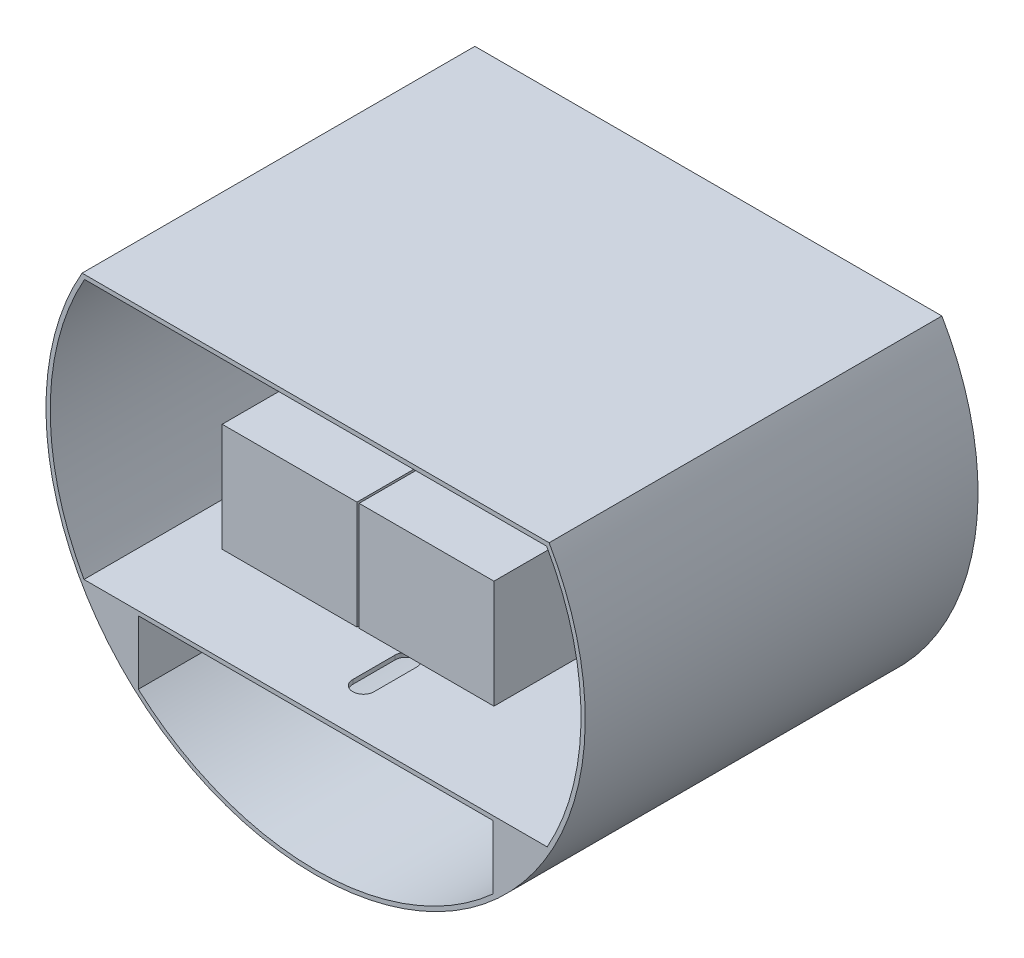
SolidWorks part; units mm, degrees
ref_plane "Front Plane" through (0, 0, 0) normal (0, 0, 1) x (1, 0, 0)
ref_plane "Top Plane" through (0, 0, 0) normal (0, 1, 0) x (1, 0, 0)
ref_plane "Right Plane" through (0, 0, 0) normal (1, 0, 0) x (0, 0, -1)
sketch "Sketch4" plane through (0, 0, 0) normal (0, 0, 1) x (1, 0, 0)
  line L0 (-109.9852, 63.5) -> (109.9852, 63.5)
  arc A0 (-109.9852, 63.5) -> (109.9852, 63.5) centre (0, 0) ccw
  point P5 (0, 63.5)
  dimension "D1" = 254
  dimension "D2" = 63.5
extrude "Exterior" add sketch "Sketch4" along normal blind 185 contours A0 L0
shell "Shell3" thickness 2 removed face at (0, -31.75, 0) removed face at (0, -31.75, 185)
sketch "Sketch7" plane through (0, 0, 0) normal (0, 0, 1) x (1, 0, 0)
  line L0 (-109.0942, -61.0202) -> (109.0942, -61.0202)
  line L1 (-83.5, -63.0202) -> (-83.5, -93.0202)
  line L2 (0, 0) -> (0, -138.9395) construction
  line L3 (83.5, -63.0202) -> (83.5, -93.0202)
  line L4 (-83.5, -63.0202) -> (83.5, -63.0202)
  arc A0 (-108.8244, 61.5) -> (108.8244, 61.5) centre (0, 0) ccw construction
  arc A1 (-109.0942, -61.0202) -> (-83.5, -93.0202) centre (0, 0) ccw
  arc A2 (83.5, -93.0202) -> (109.0942, -61.0202) centre (0, 0) ccw
  dimension "D1" = 83.5
  dimension "D2" = 2
  dimension "D3" = 30
extrude "Boss-Extrude4" add sketch "Sketch7" along normal up to surface (185 mm away) up to face at (0, -31.75, 185)
sketch "Sketch6" plane through (0, 0, 0) normal (0, 0, 1) x (1, 0, 0)
  line L0 (-64, -36.1655) -> (-0.5, -36.1655)
  line L1 (-0.5, -36.1655) -> (-0.5, 14.8345)
  line L2 (-0.5, 14.8345) -> (-64, 14.8345)
  line L3 (-64, 14.8345) -> (-64, -36.1655)
  line L12 (0.5, -36.1655) -> (64, -36.1655)
  line L13 (64, -36.1655) -> (64, 14.8345)
  line L14 (64, 14.8345) -> (0.5, 14.8345)
  line L15 (0.5, 14.8345) -> (0.5, -36.1655)
  line L20 (-0.5, 14.8345) -> (0.5, 14.8345) construction
  point P8 (0, 14.8345)
  dimension "D1" = 63.5
  dimension "D2" = 51
  dimension "D3" = 1
extrude "Batteries" add sketch "Sketch6" along normal blind 165 separate body
sketch "Sketch8" plane through (0, -61.0202, 0) normal (0, 1, 0) x (1, 0, 0)
  line L0 (-5, -22.5) -> (-5, -42.5)
  line L1 (-5, -62.5) -> (-5, -82.5)
  line L2 (-5, -82.5) -> (-5, -102.5) construction
  line L3 (-5, -102.5) -> (-5, -122.5)
  line L4 (-109.0942, -185) -> (-109.0942, 0) construction
  line L5 (-5, -142.5) -> (-5, -162.5)
  line L6 (-109.0942, -185) -> (-109.0942, 0) construction
  line L7 (5, -22.5) -> (5, -42.5)
  line L8 (5, -62.5) -> (5, -82.5)
  line L9 (5, -102.5) -> (5, -122.5)
  line L10 (5, -142.5) -> (5, -162.5)
  line L11 (-5, -22.5) -> (5, -22.5) construction
  line L12 (-5, -42.5) -> (5, -42.5) construction
  line L13 (-5, -142.5) -> (5, -142.5) construction
  line L14 (-5, -62.5) -> (5, -62.5) construction
  line L16 (-5, -82.5) -> (5, -82.5) construction
  arc A0 (5, -22.5) -> (-5, -22.5) centre (0, -22.5) ccw
  arc A1 (-5, -42.5) -> (5, -42.5) centre (0, -42.5) ccw
  arc A2 (5, -62.5) -> (-5, -62.5) centre (0, -62.5) ccw
  arc A3 (-5, -82.5) -> (5, -82.5) centre (0, -82.5) ccw
  arc A4 (5, -102.5) -> (-5, -102.5) centre (0, -102.5) ccw
  arc A5 (-5, -122.5) -> (5, -122.5) centre (0, -122.5) ccw
  arc A7 (-5, -162.5) -> (5, -162.5) centre (0, -162.5) ccw
  arc A8 (5, -142.5) -> (-5, -142.5) centre (0, -142.5) ccw
  point P10 (-109.0942, -92.5)
  point P11 (-5, -92.5)
  dimension "D1" = 20
  dimension "D2" = 20
  dimension "D3" = 20
  dimension "D4" = 20
  dimension "D5" = 10
extrude "Cut-Extrude1" cut sketch "Sketch8" against normal up to next (2 mm away)
equation "\"fuse_diam\"= 0.254"
equation "\"fuse_rad\"= 0.127"
equation "\"battery_length\"= 0.165"
equation "\"battery_width\"= 0.0635"
equation "\"battery_height\"= 0.051"
equation "\"bat_bay_length\"= 0.185"
equation "\"wing_shlef\"= 0.0635"
equation "\"shell\"= 0.002"
equation "\"D1@Sketch4\"=\"fuse_diam\""
equation "\"D1@Exterior\" = \"bat_bay_length\""
equation "\"D1@Shell3\"=\"shell\""
equation "\"D1@Sketch6\"=\"battery_width\""
equation "\"D2@Sketch6\"=\"battery_height\""
equation "\"D1@Batteries\" = \"battery_length\""
equation "\"D2@Sketch4\"=\"wing_shlef\""
equation "\"D1@Sketch7\"=\"battery_width\"+0.02"
